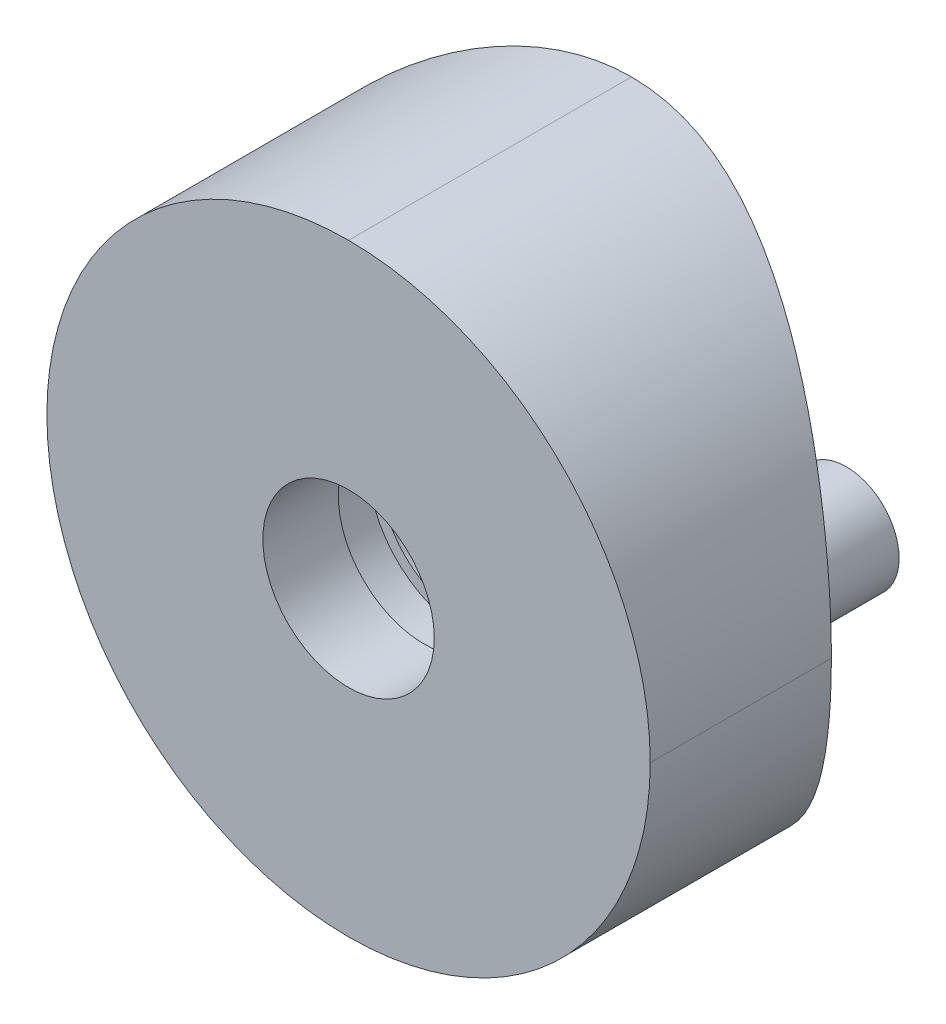
SolidWorks part; units mm, degrees
ref_plane "Front Plane" through (0, 0, 0) normal (0, 0, 1) x (1, 0, 0)
ref_plane "Top Plane" through (0, 0, 0) normal (0, 1, 0) x (1, 0, 0)
ref_plane "Right Plane" through (0, 0, 0) normal (1, 0, 0) x (0, 0, -1)
sketch "Sketch3" plane through (0, 0, 0) normal (1, 0, 0) x (0, 0, -1)
  line L0 (0, 20) -> (-9.38, 20)
  line L1 (-9.38, 20) -> (-9.38, 0)
  line L2 (-9.38, 0) -> (0, 0)
  arc A0 (0, 0) -> (0, 20) centre (13.1244, 10) cw
  dimension "D1" = 16.5
  dimension "D2" = 20
  dimension "D3" = 9.38
extrude "Boss-Extrude2" add sketch "Sketch3" along normal blind 20
fillet "Fillet1" radius 10 4 edges at (20, 0, 4.69) (0, 0, 4.69) (20, 20, 4.69) (0, 20, 4.69)
sketch "Sketch4" plane through (0, 0, 9.38) normal (0, 0, 1) x (1, 0, 0)
  circle A0 centre (10, 10) radius 2.8408
  arc A1 (10, 20) -> (0, 10) centre (10, 10) ccw construction
  dimension "D1" = 5.6816
extrude "Cut-Extrude2" cut sketch "Sketch4" against normal up to surface (6.0044 mm away) up to face at (10, 10, 1.747)
sketch "Sketch5" plane through (0, 0, 9.38) normal (0, 0, 1) x (1, 0, 0)
  circle A0 centre (10, 10) radius 3.2184
  dimension "D1" = 6.4369
extrude "Cut-Extrude3" cut sketch "Sketch5" against normal offset from surface (1.38 mm away) 5.5 from offset 2.5 up to plane "Front Plane" offset against normal yes
sketch "Sketch6" plane through (0, 0, 9.38) normal (0, 0, 1) x (1, 0, 0)
  line L0 (10, 12.8408) -> (10, 7.1592) construction
  circle A0 centre (3.5, 10) radius 1.75
  circle A1 centre (10, 10) radius 2.8408 construction
  circle A2 centre (10, 10) radius 2.8408 construction
  circle A3 centre (16.5, 10) radius 1.75
  dimension "D2" = 3.5
  dimension "D1" = 6.5
extrude "Boss-Extrude3" add sketch "Sketch6" against normal blind 4 from offset 6 offset against normal yes
